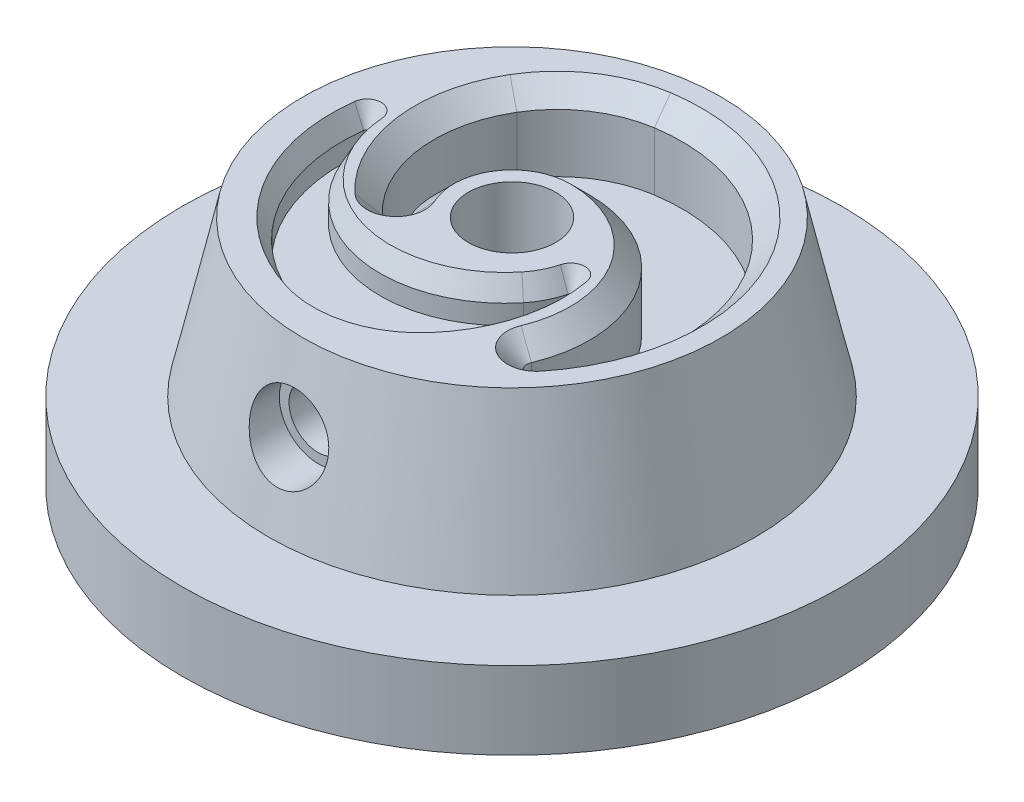
SolidWorks part; units mm, degrees
ref_plane "Front Plane" through (0, 0, 0) normal (0, 0, 1) x (1, 0, 0)
ref_plane "Top Plane" through (0, 0, 0) normal (0, 1, 0) x (1, 0, 0)
ref_plane "Right Plane" through (0, 0, 0) normal (1, 0, 0) x (0, 0, -1)
sketch "Sketch1" plane through (0, 0, 0) normal (0, 1, 0) x (1, 0, 0)
  circle A0 centre (0, 0) radius 13
  dimension "D1" = 26
extrude "Boss-Extrude1" add sketch "Sketch1" along normal blind 10
sketch "Sketch2" plane through (0, 0, 0) normal (1, 0, 0) x (0, 0, -1)
  line L0 (-13, 0) -> (-10.7714, 10)
  line L1 (13, 10) -> (-13, 10) construction
  line L2 (-10.7714, 10) -> (-13, 10)
  line L3 (-13, 10) -> (-13, 0)
  line L4 (0, 0) -> (0, 50000) construction
  line L5 (-13, 0) -> (13, 0) construction
  point P11 (0, 0)
  dimension "D1" = 12.563
revolve "Cut-Revolve1" cut sketch "Sketch2" angle 360 about L4
sketch "Sketch3" plane through (0, 0, 0) normal (0, -1, 0) x (-1, 0, 0)
  circle A0 centre (0, 0) radius 17
  dimension "D1" = 34
extrude "Boss-Extrude2" add sketch "Sketch3" along normal blind 2
sketch "Sketch4" [suppressed] plane through (0, -2, 0) normal (0, -1, 0) x (1, 0, 0)
  line L0 (1.145, -2.3899) -> (1.145, 2.3899)
  line L1 (-1.145, -2.3899) -> (-1.145, 2.3899)
  line L2 (0, 0) -> (35355.3391, 35355.3391) construction
  line L3 (0.8543, 0) -> (50000.8543, 0) construction
  line L4 (-2.3899, 1.145) -> (2.3899, 1.145)
  line L5 (-2.3899, -1.145) -> (2.3899, -1.145)
  circle A0 centre (0, 0) radius 2.65
  dimension "D1" = 5.3
  dimension "D2" = 2.29
  dimension "D3" = 45
extrude "Cut-Extrude1" [suppressed] cut sketch "Sketch4" against normal through all contours L1 L5 L0 L4 | L4 A0 L5 L1 | L0 A0 L1 L4 | L5 A0 L4 L0 | L1 A0 L0 L5
fillet "Fillet1" [suppressed] radius 0.5
sketch "Sketch5" plane through (0, 10, 0) normal (0, 1, 0) x (1, 0, 0)
  line L0 (-1.6771, 1.5) -> (1.6771, 1.5)
  circle A0 centre (0, 0) radius 2.25
  dimension "D1" = 4.5
  dimension "D2" = 1.5
extrude "4-mm shaft hole" cut sketch "Sketch5" against normal through all contours L0 A0 | A0 region at (0, 10, 0.222)
ref_plane "Plane1" through (0, 2.7601, 12.3849) normal (0, 0.2175, 0.9761) x (1, 0, 0)
sketch "Sketch7" [suppressed] plane through (0, 10, 0) normal (0, 1, 0) x (1, 0, 0)
  circle A0 centre (0, -9.7714) radius 1.6
  circle A1 centre (0, 0) radius 9.7714 construction
  circle A2 centre (0, 0) radius 10.7714 construction
  dimension "D1" = 3.2
  dimension "D2" = 1
sketch "Sketch8" [suppressed] plane through (0, 0, 0) normal (0, 1, 0) x (1, 0, 0)
  circle A0 centre (0, -12) radius 1.6
  circle A1 centre (0, 0) radius 12 construction
  circle A2 centre (0, 0) radius 13 construction
  circle A4 centre (0, -9.7714) radius 1.6 construction
  dimension "D1" = 1
loft "Cut-Loft1" [suppressed] cut profiles "Sketch7", "Sketch8"
pattern_circular "CirPattern1" [suppressed] count 15 over 360 of bodies 106
fillet "Fillet2" [suppressed] radius 0.3
sketch "Sketch9" plane through (0, 0, 0) normal (0, 1, 0) x (1, 0, 0)
  circle A0 centre (0, 0) radius 17
  circle A1 centre (0, 0) radius 17 construction
  circle A2 centre (0, 0) radius 2.25
  circle A3 centre (0, 0) radius 2.25 construction
extrude "Boss-Extrude3" add sketch "Sketch9" along normal blind 2
sketch "Sketch10" plane through (0, 0, 0) normal (0, 0, 1) x (1, 0, 0)
  line L0 (0, 2) -> (0, 10) construction
  line L1 (17, 2) -> (-17, 2) construction
  line L2 (10.7714, 10) -> (-10.7714, 10) construction
  line L3 (2.25, 10) -> (-2.25, 10) construction
  circle A0 centre (0, 6) radius 1.5
  circle A1 centre (0, 6) radius 2
  dimension "D1" = 3
  dimension "D2" = 4
extrude "Cut-Extrude3" cut sketch "Sketch10" along normal through all contours L0 A0 | A0 L0 region at (-0.6366, 6, 0) region at (0.6366, 6, 0)
extrude "Cut-Extrude4" cut sketch "Sketch10<3>" along normal through all from offset 10
sketch "Sketch10<3>" plane through (0, 0, 0) normal (0, 0, 1) x (1, 0, 0) same geometry as "Sketch10"
sketch "Sketch11" plane through (0, 10, 0) normal (0, 1, 0) x (1, 0, 0)
  line L0 (0, 4) -> (6.5318, 4) construction
  line L1 (0, -4) -> (14.8517, -4) construction
  circle A0 centre (0, 0) radius 8.7714
  circle A1 centre (0, 0) radius 4
  circle A2 centre (0, 0) radius 10.7714 construction
  arc A3 (0, 4) -> (3, -8.2424) centre (0, -2.4888) cw
  circle A4 centre (0, 0) radius 11.9788 construction
  arc A6 (0, -4) -> (-3, 8.2424) centre (0, 2.4888) cw
  dimension "D1" = 8
  dimension "D2" = 2
  dimension "D3" = 3
  dimension "D4" = 3
extrude "Cut-Extrude5" cut sketch "Sketch11" against normal blind 4 contours A6 A1 A3 A0 region at (6.9979, 10, 4.9)
fillet "Fillet3" radius 6 1 edges at (-3, 8, -8.2424)
fillet "Fillet4" radius 0.5 2 edges at (3, 8, 8.2424) (0, 8.75, 4)
chamfer "Chamfer1" distance 1 angle 45 7 edges at (-3.3712, 10, -2.1529) (5.399, 10, -1.1106) (-3.789, 10, 2.2976) (6.1961, 10, 5.6067) (-6.4243, 10, -1.5762) (7.5977, 10, -4.3833) (-3.7685, 10, -7.7179)
sketch "Sketch14" plane through (0, 10, 0) normal (0, 1, 0) x (1, 0, 0)
  line L0 (-7.9496, 3.707) -> (-6.7428, 6.2949) construction
  line L1 (-7.9496, 3.707) -> (0, 0) construction
  line L2 (1.7352, 0) -> (50001.7352, 0) construction
  line L3 (3.1086, -2.5173) -> (7.3631, 2.7365) construction
  circle A0 centre (0, 0) radius 8.7714
  circle A1 centre (0, 0) radius 10.7714 construction
  circle A2 centre (0, 0) radius 4
  arc A3 (4, 0) -> (0, -8.7714) centre (-2.6184, -2.2796) cw
  arc A7 (3.1086, -2.5173) -> (-7.9496, 3.707) centre (-1.8927, 1.5326) cw
  dimension "D1" = 2
  dimension "D2" = 8
  dimension "D3" = 7
  dimension "D5" = 25
  dimension "D6" = 51
extrude "Cut-Extrude7" cut sketch "Sketch14" against normal blind 2 contours A2 A7 A0 A3 region at (-1.8928, 10, 5.2059)
fillet "Fillet6" radius 5 1 edges at (0, 9, 8.7714)
fillet "Fillet8" radius 0.2 2 edges at (-7.9496, 9, -3.707) (4, 9, 0)
chamfer "Chamfer3" distance 1 angle 28 7 edges at (-3.8101, 10, 4.6105) (-8.5046, 10, -1.2316) (3.5737, 10, 1.7969) (-7.3628, 10, 4.7673) (4.0751, 10, 0.8436) (0.2337, 10, 8.4158) (4.1284, 10, 4.1453) first distance on face at (-3.2053, 9, 2.6729) first distance on face at (-8.5066, 9, -1.1414) first distance on face at (3.5326, 9, 1.7762) first distance on face at (-6.5083, 9, 4.214) first distance on face at (4.0724, 9, 0.9221) first distance on face at (0.1252, 9, 8.0291) first distance on face at (3.7887, 9, 4.0514)
